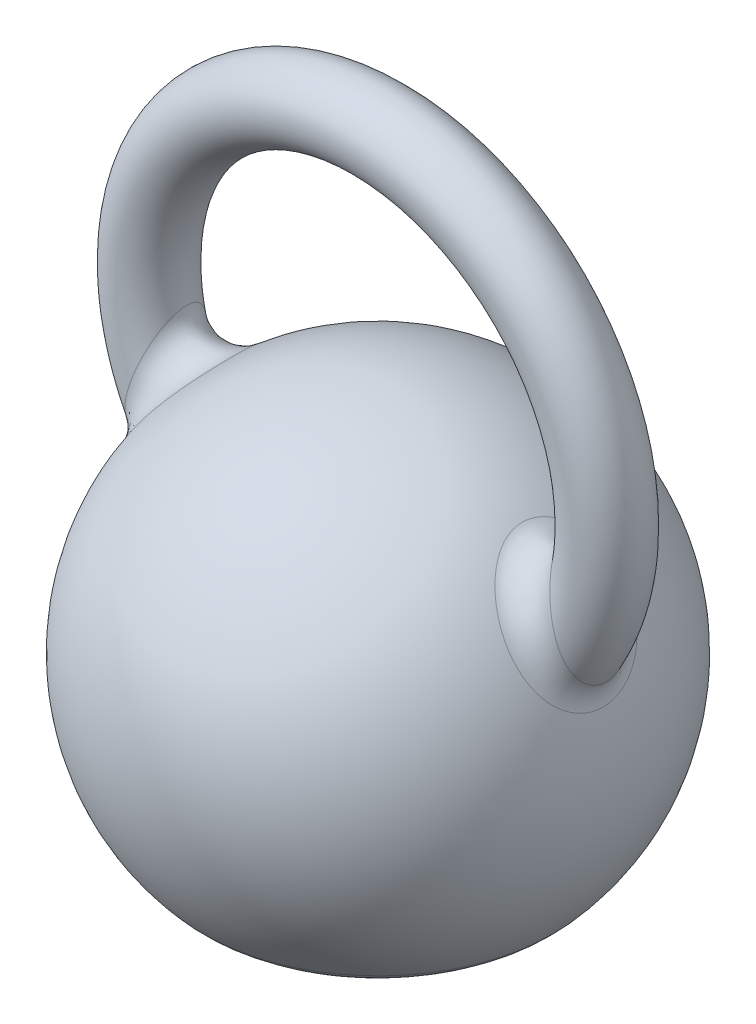
SolidWorks part; units mm, degrees
material "1060 Alloy"
ref_plane "Front Plane" through (0, 0, 0) normal (0, 0, 1) x (1, 0, 0)
ref_plane "Top Plane" through (0, 0, 0) normal (0, 1, 0) x (1, 0, 0)
ref_plane "Right Plane" through (0, 0, 0) normal (1, 0, 0) x (0, 0, -1)
sketch "Sketch1" plane through (0, 0, 0) normal (0, 0, 1) x (1, 0, 0)
  line L0 (0, -101.6) -> (0, 101.6) construction
  line L1 (0, -76.2) -> (67.2021, -76.2)
  line L2 (0, 101.6) -> (0, -76.2)
  line L3 (0, 101.6) -> (-97.0776, 101.6) construction
  line L4 (0, 0) -> (101.6, 0) construction
  ellipse E0 centre (0, 0) end of major axis (0, 101.6) minor radius 101.6 (67.2021, -76.2) -> (0, 101.6) ccw
  point P4 (0, 0)
  dimension "D1" = 101.6
  dimension "D2" = 177.8
revolve "Revolve1" add sketch "Sketch1" angle 360 about L0
fillet "Fillet1" radius 25.4 1 edges at (67.2021, -76.2, 0)
sketch "Sketch2" plane through (0, 0, 0) normal (0, 0, 1) x (1, 0, 0)
  line L0 (0, 0) -> (0, 196.4885) construction
  line L1 (0, 196.4885) -> (-45.1729, 196.4885) construction
  arc A0 (0, 196.4885) -> (78.4036, 36.5845) centre (0, 97.3152) cw
ref_plane "Plane1" through (78.4036, 36.5845, 0) normal (-0.6124, -0.7906, 0) x (-0.7906, 0.6124, 0)
sketch "Sketch3" plane through (78.4036, 36.5845, 0) normal (-0.6124, -0.7906, 0) x (-0.7906, 0.6124, 0)
  line L0 (0, 0) -> (159.904, 0) construction
  circle A0 centre (0, 0) radius 15.875
  dimension "D1" = 31.75
sweep "Sweep1" add profiles "Sketch3" path "Sketch2"
mirror "Mirror1" about plane through (0, 0, 0) normal (1, 0, 0) of "Sweep1"
fillet "Fillet2" radius 12.7 2 edges at (77.359, 65.8095, 2.6943) (-95.6294, 34.1212, 3.6492)
